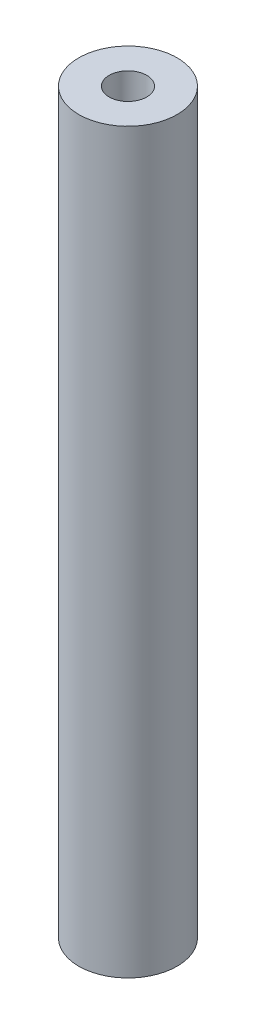
SolidWorks part; units mm, degrees
ref_plane "Front Plane" through (0, 0, 0) normal (0, 0, 1) x (1, 0, 0)
ref_plane "Top Plane" through (0, 0, 0) normal (0, 1, 0) x (1, 0, 0)
ref_plane "Right Plane" through (0, 0, 0) normal (1, 0, 0) x (0, 0, -1)
sketch "Sketch1" plane through (0, 0, 0) normal (0, 1, 0) x (1, 0, 0)
  circle A0 centre (0, 0) radius 2
  circle A1 centre (0, 0) radius 0.765
  dimension "D1" = 4
  dimension "D2" = 1.53
extrude "Boss-Extrude1" add sketch "Sketch1" along normal mid plane 30
